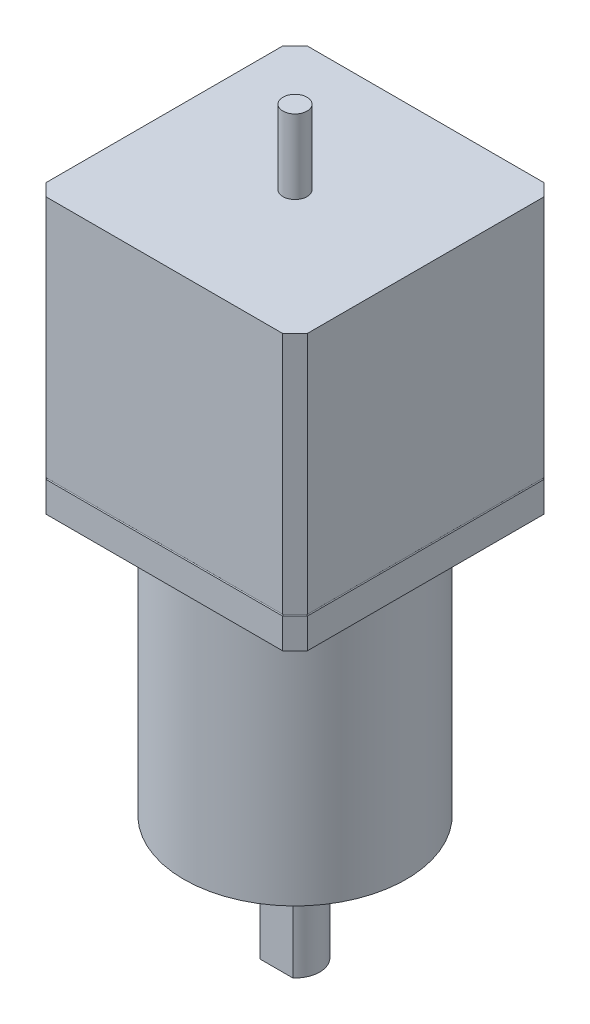
SolidWorks part; units mm, degrees
ref_plane "Front Plane" through (0, 0, 0) normal (0, 0, 1) x (1, 0, 0)
ref_plane "Top Plane" through (0, 0, 0) normal (0, 1, 0) x (1, 0, 0)
ref_plane "Right Plane" through (0, 0, 0) normal (1, 0, 0) x (0, 0, -1)
sketch "Sketch1" plane through (0, 0, 0) normal (0, 1, 0) x (1, 0, 0)
  line L1 (0, 0) -> (-42.3, 0)
  line L2 (0, 0) -> (0, -42.3)
  line L3 (0, -42.3) -> (-42.3, -42.3)
  line L4 (-42.3, 0) -> (-42.3, -42.3)
  dimension "D1" = 42.3
  dimension "D2" = 42.3
extrude "Boss-Extrude1" add sketch "Sketch1" along normal blind 44.5
chamfer "Chamfer1" distance 2 angle 45 4 edges at (-42.3, 22.25, 42.3) (0, 22.25, 42.3) (0, 22.25, 0) (-42.3, 22.25, 0)
sketch "Sketch3" plane through (0, 44.5, 0) normal (0, 1, 0) x (1, 0, 0)
  line L0 (-21.15, 0) -> (-21.15, -42.3) construction
  line L1 (-2, 0) -> (-40.3, 0) construction
  line L2 (-40.3, -42.3) -> (-2, -42.3) construction
  circle A0 centre (-21.15, -21.15) radius 1.95
  dimension "D1" = 3.9
extrude "Boss-Extrude2" add sketch "Sketch3" along normal blind 12
sketch "Sketch4" plane through (0, 0, 0) normal (0, -1, 0) x (1, 0, 0)
  line L0 (-21.15, 42.3) -> (-21.15, 0) construction
  line L1 (-40.3, 42.3) -> (-2, 42.3) construction
  line L2 (-2, 0) -> (-40.3, 0) construction
  circle A0 centre (-21.15, 21.15) radius 18
  dimension "D1" = 36
extrude "Boss-Extrude3" add sketch "Sketch4" along normal blind 43.2
ref_plane "Plane1" through (0, 5, 0) normal (0, -1, 0) x (-1, 0, 0)
sketch "Sketch5" plane through (0, 5, 0) normal (0, -1, 0) x (-1, 0, 0)
  line L0 (2, 0) -> (0, -2) construction
  line L1 (0, -40.3) -> (0, -2) construction
  line L2 (0, -40.3) -> (2, -42.3) construction
  line L3 (40.3, -42.3) -> (2, -42.3) construction
  line L4 (40.3, -42.3) -> (42.3, -40.3) construction
  line L5 (42.3, -2) -> (42.3, -40.3) construction
  line L6 (42.3, -2) -> (40.3, 0) construction
  line L7 (2, 0) -> (40.3, 0) construction
  line L8 (2, 0) -> (0, -2)
  line L9 (0, -40.3) -> (0, -2)
  line L10 (0, -40.3) -> (2, -42.3)
  line L11 (40.3, -42.3) -> (2, -42.3)
  line L12 (40.3, -42.3) -> (42.3, -40.3)
  line L13 (42.3, -2) -> (42.3, -40.3)
  line L14 (42.3, -2) -> (40.3, 0)
  line L15 (2, 0) -> (40.3, 0)
sketch "Sketch6" plane through (0, 0, 0) normal (1, 0, 0) x (0, 0, -1)
  line L0 (-40.3, 5) -> (-42.3, 5) construction
  line L1 (-40.3, 44.5) -> (-40.3, 0) construction
  circle A0 centre (-40.3, 5) radius 0.125
  point P2 (-42.2023, 4.7035)
  point P3 (0, 0)
  point P6 (-40.3, 5)
  dimension "D1" = 0.25
sweep "Cut-Sweep2" cut profiles "Sketch6" path "Sketch5"
sketch "Sketch7" plane through (0, -43.2, 0) normal (0, -1, 0) x (1, 0, 0)
  line L0 (-21.15, 21.15) -> (-21.15, 39.15) construction
  circle A0 centre (-21.15, 21.15) radius 18 construction
  circle A1 centre (-21.15, 21.15) radius 11
  point P7 (0, 0)
  point P8 (0, 0)
  point P9 (-21.1165, 21.15)
  dimension "D1" = 22
extrude "Boss-Extrude4" add sketch "Sketch7" along normal blind 2 contours A1
sketch "Sketch9" plane through (0, -45.2, 0) normal (0, -1, 0) x (1, 0, 0)
  circle A0 centre (-21.15, 21.15) radius 4
  dimension "D1" = 8
extrude "Boss-Extrude5" add sketch "Sketch9" along normal blind 18
sketch "Sketch10" plane through (0, -63.2, 0) normal (0, -1, 0) x (1, 0, 0)
  line L0 (-23.7958, 24.15) -> (-18.5042, 24.15)
  line L1 (-18.5042, 24.15) -> (-18.5042, 27.15)
  line L2 (-18.5042, 27.15) -> (-23.7958, 27.15)
  line L3 (-23.7958, 27.15) -> (-23.7958, 24.15)
  line L4 (-21.15, 24.15) -> (-21.15, 17.15) construction
  circle A0 centre (-21.15, 21.15) radius 4 construction
  dimension "D1" = 7
  dimension "D2" = 3
extrude "Cut-Extrude1" cut sketch "Sketch10" against normal blind 15
sketch "Sketch11" plane through (0, -43.2, 0) normal (0, -1, 0) x (1, 0, 0)
  line L0 (-21.15, 35.15) -> (-21.15, 21.15) construction
  line L1 (-21.15, 21.15) -> (-11.2505, 31.0495) construction
  circle A0 centre (-21.15, 21.15) radius 14 construction
  dimension "D1" = 28
  dimension "D2" = 45
hole_wizard "M3 Clearance Hole1" positions "Sketch12" profile "Sketch13" hole size "M3" standard "ANSI Metric"
sketch "Sketch12" plane through (0, -43.2, 0) normal (0, -1, 0) x (-1, 0, 0)
  point P0 (11.2505, -31.0495)
sketch "Sketch13" plane through (-11.2505, -43.2, 31.0495) normal (1, 0, 0) x (0, 0, -1)
  line L0 (0, 0) -> (0, 21.0215)
  line L1 (0, 21.0215) -> (1.7, 20)
  line L2 (1.7, 20) -> (1.7, 0.025)
  line L3 (1.7, 0.025) -> (1.725, 0)
  line L5 (1.725, 0) -> (0, 0)
  line L6 (-1.7, 0.025) -> (-1.725, 0) construction
  line L10 (0, 21.0215) -> (-1.7, 20) construction
  line L11 (0, -6.35) -> (0, 107.95) construction
  dimension "Hole Dia." = 3.4
  dimension "Hole Depth" = 20
  dimension "Near C'Sink Dia." = 3.45
  dimension "Near C'Sink Angle" = 90
  dimension "Drill Angle" = 118
pattern_circular "CirPattern1" count 4 over 360 about axis through (-21.15, -43.2, 21.15) along (0, -1, 0) of "M3 Clearance Hole1"
